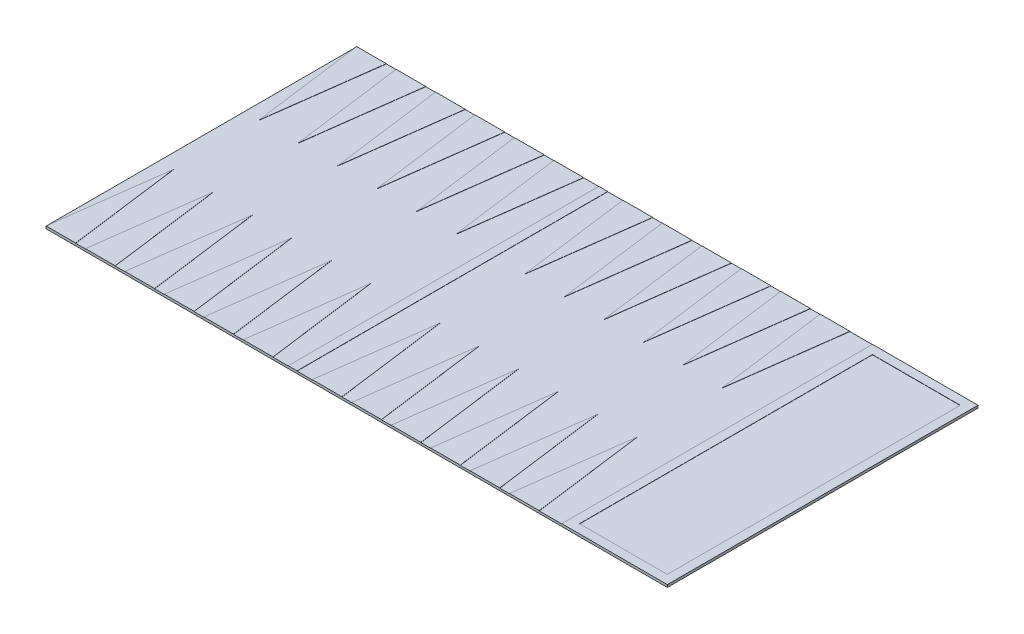
SolidWorks part; units mm, degrees
ref_plane "Front Plane" through (0, 0, 0) normal (0, 0, 1) x (1, 0, 0)
ref_plane "Top Plane" through (0, 0, 0) normal (0, 1, 0) x (1, 0, 0)
ref_plane "Right Plane" through (0, 0, 0) normal (1, 0, 0) x (0, 0, -1)
sketch "Sketch1" plane through (0, 0, 0) normal (0, 1, 0) x (1, 0, 0)
  line L1 (-350, -175) -> (350, -175)
  line L2 (-350, -175) -> (-350, 175)
  line L3 (-350, 175) -> (350, 175)
  line L4 (350, -175) -> (350, 175)
  line L5 (-350, -175) -> (350, 175) construction
  line L6 (-350, 175) -> (350, -175) construction
  point P0 (0, 0)
  dimension "D1" = 700
  dimension "D2" = 350
extrude "Boss-Extrude1" add sketch "Sketch1" along normal blind 2.54
sketch "Sketch2" plane through (0, 2.54, 0) normal (0, 1, 0) x (1, 0, 0)
  line L0 (275, 175) -> (275, -175) construction
  line L1 (350, 175) -> (-350, 175) construction
  line L2 (-350, -175) -> (350, -175) construction
  line L3 (350, -175) -> (350, 175) construction
  line L4 (-350, 175) -> (-333.2801, 48)
  line L5 (-333.2801, 48) -> (-316.5603, 175)
  line L6 (-333.2801, 48) -> (-333.2801, 175) construction
  line L7 (-350, 175) -> (-316.5603, 175)
  line L23 (-305.55, 175) -> (-272.1103, 175)
  line L24 (-288.8301, 48) -> (-272.1103, 175)
  line L25 (-305.55, 175) -> (-288.8301, 48)
  line L26 (-261.1, 175) -> (-227.6603, 175)
  line L27 (-244.3801, 48) -> (-227.6603, 175)
  line L28 (-261.1, 175) -> (-244.3801, 48)
  line L29 (-216.65, 175) -> (-183.2103, 175)
  line L30 (-199.9301, 48) -> (-183.2103, 175)
  line L31 (-216.65, 175) -> (-199.9301, 48)
  line L32 (-172.2, 175) -> (-138.7603, 175)
  line L33 (-155.4801, 48) -> (-138.7603, 175)
  line L34 (-172.2, 175) -> (-155.4801, 48)
  line L35 (-127.75, 175) -> (-94.3103, 175)
  line L36 (-111.0301, 48) -> (-94.3103, 175)
  line L37 (-127.75, 175) -> (-111.0301, 48)
  line L38 (-350, 0) -> (350, 0) construction
  line L39 (-350, 175) -> (-350, -175) construction
  line L40 (-333.2801, -48) -> (-333.2801, -175) construction
  line L41 (-127.75, -175) -> (-111.0301, -48)
  line L42 (-111.0301, -48) -> (-94.3103, -175)
  line L43 (-127.75, -175) -> (-94.3103, -175)
  line L44 (-172.2, -175) -> (-155.4801, -48)
  line L45 (-155.4801, -48) -> (-138.7603, -175)
  line L46 (-172.2, -175) -> (-138.7603, -175)
  line L47 (-216.65, -175) -> (-199.9301, -48)
  line L48 (-199.9301, -48) -> (-183.2103, -175)
  line L49 (-216.65, -175) -> (-183.2103, -175)
  line L50 (-261.1, -175) -> (-244.3801, -48)
  line L51 (-244.3801, -48) -> (-227.6603, -175)
  line L52 (-261.1, -175) -> (-227.6603, -175)
  line L53 (-305.55, -175) -> (-288.8301, -48)
  line L54 (-288.8301, -48) -> (-272.1103, -175)
  line L55 (-305.55, -175) -> (-272.1103, -175)
  line L56 (-350, -175) -> (-316.5603, -175)
  line L57 (-333.2801, -48) -> (-316.5603, -175)
  line L58 (-350, -175) -> (-333.2801, -48)
  line L59 (-50.026, 175) -> (-33.3061, 48)
  line L60 (-33.3061, 48) -> (-16.5863, 175)
  line L61 (-50.026, 175) -> (-16.5863, 175)
  line L62 (-5.576, 175) -> (27.8637, 175)
  line L63 (11.1439, 48) -> (27.8637, 175)
  line L64 (-5.576, 175) -> (11.1439, 48)
  line L65 (38.874, 175) -> (72.3137, 175)
  line L66 (55.5939, 48) -> (72.3137, 175)
  line L67 (38.874, 175) -> (55.5939, 48)
  line L68 (83.324, 175) -> (116.7637, 175)
  line L69 (100.0439, 48) -> (116.7637, 175)
  line L70 (83.324, 175) -> (100.0439, 48)
  line L71 (127.774, 175) -> (161.2137, 175)
  line L72 (144.4939, 48) -> (161.2137, 175)
  line L73 (127.774, 175) -> (144.4939, 48)
  line L74 (172.224, 175) -> (205.6637, 175)
  line L75 (188.9439, 48) -> (205.6637, 175)
  line L76 (172.224, 175) -> (188.9439, 48)
  line L77 (172.224, -175) -> (188.9439, -48)
  line L78 (188.9439, -48) -> (205.6637, -175)
  line L79 (172.224, -175) -> (205.6637, -175)
  line L80 (127.774, -175) -> (144.4939, -48)
  line L81 (144.4939, -48) -> (161.2137, -175)
  line L82 (127.774, -175) -> (161.2137, -175)
  line L83 (83.324, -175) -> (100.0439, -48)
  line L84 (100.0439, -48) -> (116.7637, -175)
  line L85 (83.324, -175) -> (116.7637, -175)
  line L86 (38.874, -175) -> (55.5939, -48)
  line L87 (55.5939, -48) -> (72.3137, -175)
  line L88 (38.874, -175) -> (72.3137, -175)
  line L89 (-5.576, -175) -> (11.1439, -48)
  line L90 (11.1439, -48) -> (27.8637, -175)
  line L91 (-5.576, -175) -> (27.8637, -175)
  line L92 (-50.026, -175) -> (-16.5863, -175)
  line L93 (-33.3061, -48) -> (-16.5863, -175)
  line L94 (-50.026, -175) -> (-33.3061, -48)
  line L95 (-33.3061, 48) -> (-33.3061, 175) construction
  line L96 (-33.3061, -48) -> (-33.3061, -175) construction
  line L97 (-94.3103, 175) -> (-50.026, 175) construction
  line L98 (-77.1681, -175) -> (-67.1681, -175)
  line L99 (-77.1681, -175) -> (-77.1681, 175)
  line L100 (-77.1681, 175) -> (-67.1681, 175)
  line L101 (-67.1681, -175) -> (-67.1681, 175)
  line L102 (-77.1681, -175) -> (-67.1681, 175) construction
  line L103 (-77.1681, 175) -> (-67.1681, -175) construction
  line L105 (231.0637, -175) -> (241.0637, -175)
  line L106 (231.0637, -175) -> (231.0637, 175)
  line L107 (231.0637, 175) -> (241.0637, 175)
  line L108 (241.0637, -175) -> (241.0637, 175)
  line L109 (231.0637, -175) -> (241.0637, 175) construction
  line L110 (231.0637, 175) -> (241.0637, -175) construction
  line L111 (241.0637, 175) -> (350, 175)
  line L112 (241.0637, 175) -> (241.0637, 165)
  line L113 (241.0637, 165) -> (350, 165)
  line L114 (350, 175) -> (350, 165)
  line L115 (241.0637, -175) -> (350, -175)
  line L116 (241.0637, -175) -> (241.0637, -165)
  line L117 (241.0637, -165) -> (350, -165)
  line L118 (350, -175) -> (350, -165)
  line L119 (350, -165) -> (340, -165)
  line L120 (350, -165) -> (350, 165)
  line L121 (350, 165) -> (340, 165)
  line L122 (340, -165) -> (340, 165)
  point P51 (-72.1681, 0)
  point P94 (-72.1681, 175)
  point P95 (236.0637, 0)
  point P108 (0, 0)
  point P109 (0, 0)
  line M48 (350, -175) -> (350, 175)
  line M49 (350, 175) -> (-350, 175)
  line M51 (-350, -175) -> (350, -175)
  dimension "D1" = 75
  dimension "D2" = 7.5
  dimension "D3" = 127
  dimension "D6" = 10
  dimension "D7" = 10
  dimension "D8" = 10
  dimension "D9" = 10
  dimension "D10" = 10
  dimension "D11" = 25.4
  dimension "D4" = 6
  dimension "D5" = 2
extrude "Boss-Extrude2" add sketch "Sketch2" along normal blind 0.254 contours L4 L5 M49 | L25 L24 M49 | L28 L27 M49 | L31 L30 M49 | L34 L33 M49 | L37 L36 M49 | L101 L99 M51 M49 | L59 L60 M49 | L64 L63 M49 | L67 L66 M49 | L70 L69 M49 | L73 L72 M49 | L76 L75 M49 | L58 L57 M51 | L54 L53 M51 | L51 L50 M51 | L48 L47 M51 | L45 L44 M51 | L42 L41 M51 | L94 L93 M51 | L90 L89 M51 | L87 L86 M51 | L84 L83 M51 | L81 L80 M51 | L78 L77 M51 | L108 L106 M51 M49 | L117 L108 M51 M48 | L122 L117 L113 M48 | L108 L113 M48 M49 region at (-333.2801, 2.54, -132.6667) region at (-333.2801, 2.54, 132.6667) region at (-288.8301, 2.54, 132.6667) region at (-244.3801, 2.54, 132.6667) region at (-199.9301, 2.54, 132.6667) region at (-155.4801, 2.54, 132.6667) region at (-111.0301, 2.54, 132.6667) region at (-72.1681, 2.54, 0) region at (-111.0301, 2.54, -132.6667) region at (-155.4801, 2.54, -132.6667) region at (-199.9301, 2.54, -132.6667) region at (-244.3801, 2.54, -132.6667) region at (-288.8301, 2.54, -132.6667) region at (-33.3061, 2.54, -132.6667) region at (-33.3061, 2.54, 132.6667) region at (11.1439, 2.54, -132.6667) region at (11.1439, 2.54, 132.6667) region at (55.5939, 2.54, -132.6667) region at (55.5939, 2.54, 132.6667) region at (100.0439, 2.54, -132.6667) region at (100.0439, 2.54, 132.6667) region at (144.4939, 2.54, -132.6667) region at (144.4939, 2.54, 132.6667) region at (188.9439, 2.54, -132.6667) region at (188.9439, 2.54, 132.6667) region at (236.0637, 2.54, 0) region at (295.5319, 2.54, -170) region at (295.5319, 2.54, 170) region at (345, 2.54, 0)
